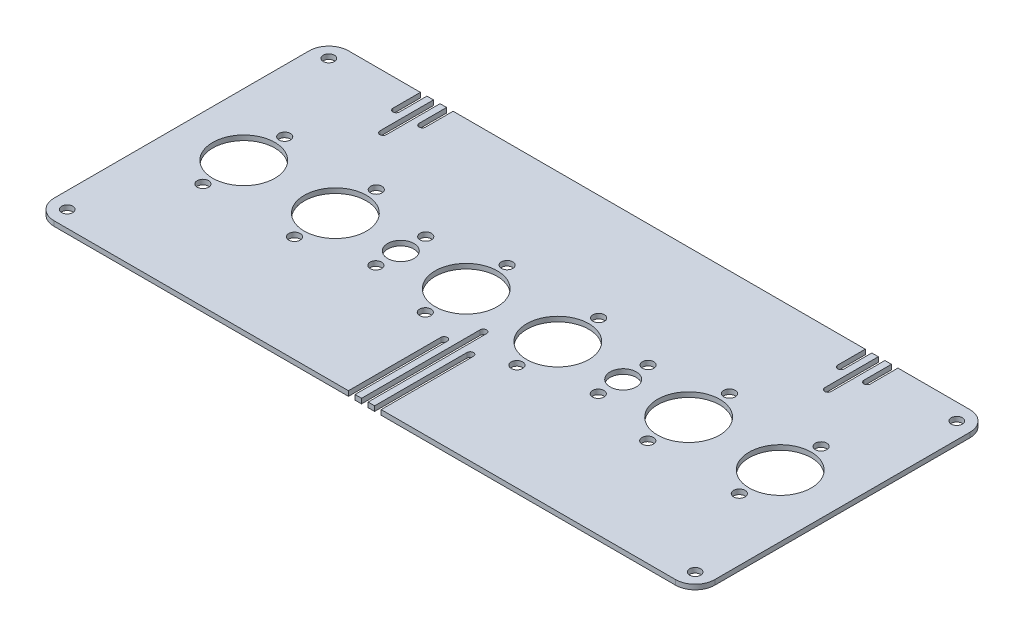
SolidWorks part; units mm, degrees
ref_plane "Plan de face" through (0, 0, 0) normal (0, 0, 1) x (1, 0, 0)
ref_plane "Plan de dessus" through (0, 0, 0) normal (0, 1, 0) x (1, 0, 0)
ref_plane "Plan de droite" through (0, 0, 0) normal (1, 0, 0) x (0, 0, -1)
sketch "Esquisse1" plane through (0, 0, 0) normal (0, 1, 0) x (1, 0, 0)
  line L1 (0, -90) -> (202, -90)
  line L2 (0, -90) -> (0, 0)
  line L3 (0, 0) -> (202, 0)
  line L4 (202, -90) -> (202, 0)
  dimension "D1" = 202
  dimension "D2" = 90
extrude "Boss.-Extru.1" add sketch "Esquisse1" along normal blind 1.5
sketch "Esquisse2" plane through (0, 1.5, 0) normal (0, 1, 0) x (1, 0, 0)
  line L0 (0, -90) -> (0, 0) construction
  line L1 (0, 0) -> (0, -90) construction
  line L2 (202, -90) -> (202, 0) construction
  line L3 (0, -90) -> (202, -90) construction
  line L4 (202, -90) -> (202, 0) construction
  line L5 (0, 0) -> (202, -90) construction
  line L6 (0, -90) -> (202, 0) construction
  line L7 (19, -57.5) -> (19, -32.5) construction
  line L8 (47, -57.5) -> (47, -32.5) construction
  line L9 (87, -32.5) -> (87, -57.5) construction
  line L10 (115, -57.5) -> (115, -32.5) construction
  line L11 (155, -57.5) -> (155, -32.5) construction
  line L12 (183, -57.5) -> (183, -32.5) construction
  line L13 (67, -52.62) -> (67, -37.38) construction
  line L14 (135, -52.62) -> (135, -37.38) construction
  line L15 (202, 0) -> (0, 0) construction
  circle A0 centre (115, -45) radius 9.5
  circle A1 centre (87, -45) radius 9.5
  circle A2 centre (155, -45) radius 9.5
  circle A3 centre (183, -45) radius 9.5
  circle A4 centre (47, -45) radius 9.5
  circle A5 centre (19, -45) radius 9.5
  circle A6 centre (67, -45) radius 4
  circle A7 centre (135, -45) radius 4
  circle A8 centre (19, -57.5) radius 1.75
  circle A9 centre (19, -32.5) radius 1.75
  circle A10 centre (47, -57.5) radius 1.75
  circle A11 centre (47, -32.5) radius 1.75
  circle A12 centre (87, -57.5) radius 1.75
  circle A13 centre (87, -32.5) radius 1.75
  circle A14 centre (115, -32.5) radius 1.75
  circle A15 centre (115, -57.5) radius 1.75
  circle A16 centre (155, -57.5) radius 1.75
  circle A17 centre (155, -32.5) radius 1.75
  circle A18 centre (183, -32.5) radius 1.75
  circle A19 centre (183, -57.5) radius 1.75
  circle A20 centre (67, -52.62) radius 1.75
  circle A21 centre (67, -37.38) radius 1.75
  circle A22 centre (135, -37.38) radius 1.75
  circle A23 centre (135, -52.62) radius 1.75
  point P15 (101, -45)
  point P33 (19, -45)
  point P54 (183, -45)
  dimension "D2" = 19
  dimension "D9" = 8
  dimension "D12" = 3.5
  dimension "D3" = 14
  dimension "D4" = 14
  dimension "D5" = 28
  dimension "D6" = 40
  dimension "D7" = 40
  dimension "D8" = 28
  dimension "D10" = 20
  dimension "D11" = 20
  dimension "D13" = 15.24
  dimension "D14" = 25
extrude "Enlèv. mat.-Extru.1" cut sketch "Esquisse2" against normal up to next
hole_wizard "Dégagement M31" positions "Esquisse3" profile "Esquisse4" hole size "M3" standard "ISO" end condition through all
sketch "Esquisse3" plane through (0, 0, 0) normal (0, -1, 0) x (-1, 0, 0)
  line L0 (-5, -85) -> (-197, -85) construction
  line L1 (-197, -85) -> (-197, -5) construction
  line L2 (-197, -5) -> (-5, -5) construction
  line L3 (-5, -5) -> (-5, -85) construction
  line L4 (0, 0) -> (-202, 0) construction
  line L6 (-5, -5) -> (-197, -85) construction
  line L7 (-202, 0) -> (0, -90) construction
  point P0 (-5, -85)
  point P2 (-5, -5)
  point P4 (-197, -5)
  point P6 (-197, -85)
  point P41 (-101, -45)
  dimension "D1" = 192
  dimension "D2" = 80
sketch "Esquisse4" plane through (5, 0, 85) normal (1, 0, 0) x (0, 0, -1)
  line L0 (0, 0) -> (0, 1.5)
  line L1 (0, 1.5) -> (1.7, 1.5)
  line L2 (1.7, 1.5) -> (1.7, 0)
  line L5 (1.7, 0) -> (0, 0)
  line L11 (0, -6.35) -> (0, 107.95) construction
  dimension "Diamètre du perçage jusqu'au prochain" = 3.4
  dimension "Profondeur du perçage jusqu'au prochain" = 1.5
fillet "Congé1" radius 6 4 edges at (202, 0.75, 90) (0, 0.75, 90) (0, 0.75, 0) (202, 0.75, 0)
ref_plane "Plan2" through (0, 0, 45) normal (0, 0, 1) x (1, 0, 0)
ref_plane "Plan1" through (101, 0, 0) normal (-1, 0, 0) x (0, 0, 1)
sketch "Esquisse6" plane through (0, 1.5, 0) normal (0, 1, 0) x (1, 0, 0)
  line L0 (6, -90) -> (196, -90) construction
  line L1 (100, -90) -> (102, -90)
  line L2 (100, -90) -> (100, -53.7639)
  line L4 (102, -90) -> (102, -53.7639)
  line L5 (98, -61.7639) -> (100, -61.7639) construction
  line L7 (96, -61.7639) -> (96, -90)
  line L8 (96, -90) -> (98, -90)
  line L9 (98, -61.7639) -> (98, -90)
  line L11 (104, -61.7639) -> (104, -90)
  line L12 (104, -90) -> (106, -90)
  line L13 (106, -61.7639) -> (106, -90)
  line L14 (104, -61.7639) -> (102, -61.7639) construction
  line L15 (19, -45) -> (47, -45) construction
  line L16 (155, -45) -> (183, -45) construction
  line L17 (196, 0) -> (6, 0) construction
  line L18 (32, 0) -> (34, 0)
  line L19 (32, 0) -> (32, -16.4122)
  line L21 (34, 0) -> (34, -16.4122)
  line L22 (30, -8.4122) -> (32, -8.4122) construction
  line L23 (36, 0) -> (38, 0)
  line L24 (36, 0) -> (36, -8.4122)
  line L26 (38, 0) -> (38, -8.4122)
  line L27 (28, 0) -> (30, 0)
  line L28 (28, 0) -> (28, -8.4122)
  line L30 (30, 0) -> (30, -8.4122)
  line L31 (168, 0) -> (170, 0)
  line L32 (168, 0) -> (168, -16.4122)
  line L34 (170, 0) -> (170, -16.4122)
  line L35 (172, 0) -> (174, 0)
  line L36 (172, 0) -> (172, -8.4122)
  line L38 (174, 0) -> (174, -8.4122)
  line L39 (164, 0) -> (166, 0)
  line L40 (164, 0) -> (164, -8.4122)
  line L42 (166, 0) -> (166, -8.4122)
  line L43 (36, -8.4122) -> (34, -8.4122) construction
  line L44 (166, -8.4122) -> (168, -8.4122) construction
  line L45 (172, -8.4122) -> (170, -8.4122) construction
  arc A0 (100, -53.7639) -> (102, -53.7639) centre (101, -53.7639) cw
  arc A1 (96, -61.7639) -> (98, -61.7639) centre (97, -61.7639) cw
  arc A2 (104, -61.7639) -> (106, -61.7639) centre (105, -61.7639) cw
  arc A3 (30, -8.4122) -> (28, -8.4122) centre (29, -8.4122) cw
  arc A4 (32, -16.4122) -> (34, -16.4122) centre (33, -16.4122) ccw
  arc A5 (36, -8.4122) -> (38, -8.4122) centre (37, -8.4122) ccw
  arc A6 (164, -8.4122) -> (166, -8.4122) centre (165, -8.4122) ccw
  arc A7 (168, -16.4122) -> (170, -16.4122) centre (169, -16.4122) ccw
  arc A8 (172, -8.4122) -> (174, -8.4122) centre (173, -8.4122) ccw
  point P14 (101, -90)
  dimension "D1" = 2
  dimension "D2" = 2
  dimension "D3" = 8
  dimension "D4" = 8
extrude "Enlèv. mat.-Extru.3" cut sketch "Esquisse6" against normal up to next
